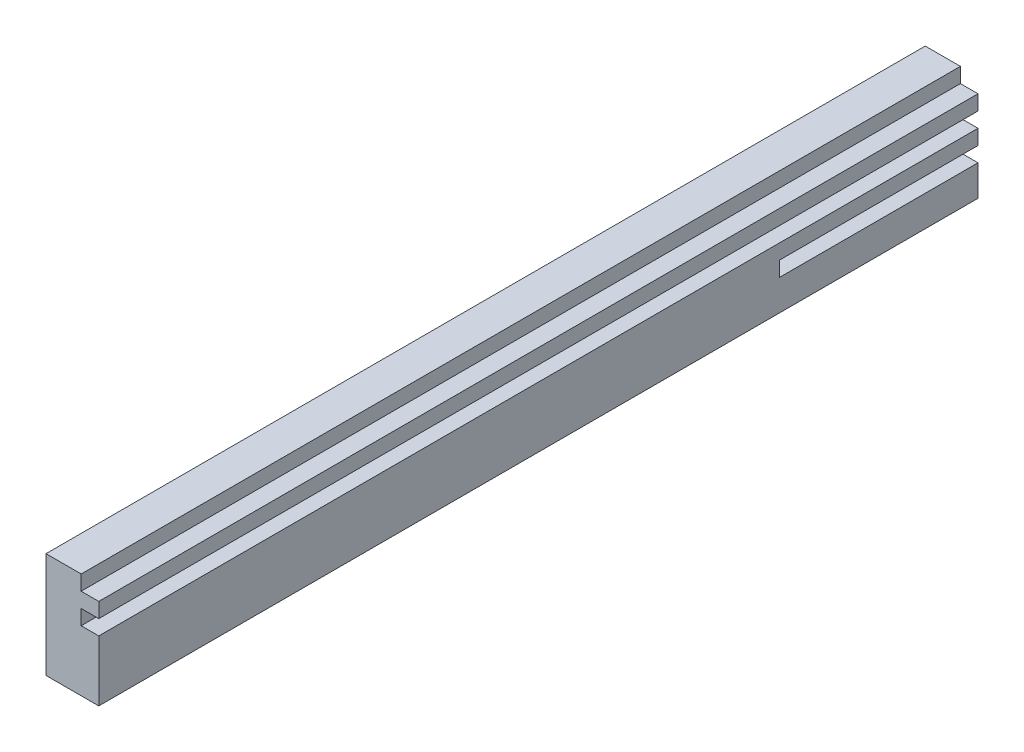
SolidWorks part; units mm, degrees
ref_plane "Front Plane" through (0, 0, 0) normal (0, 0, 1) x (1, 0, 0)
ref_plane "Top Plane" through (0, 0, 0) normal (0, 1, 0) x (1, 0, 0)
ref_plane "Right Plane" through (0, 0, 0) normal (1, 0, 0) x (0, 0, -1)
sketch "Sketch1" plane through (0, 0, 0) normal (1, 0, 0) x (0, 0, -1)
  line L1 (0, 0) -> (500, 0)
  line L2 (0, 0) -> (0, 60)
  line L3 (0, 60) -> (500, 60)
  line L4 (500, 0) -> (500, 60)
  dimension "D1" = 60
  dimension "D2" = 500
extrude "Boss-Extrude1" add sketch "Sketch1" along normal blind 30
sketch "Sketch2" plane through (30, 0, 0) normal (1, 0, 0) x (0, 0, -1)
  line L0 (500, 0) -> (500, 60) construction
  line L1 (0, 60) -> (500, 60)
  line L2 (0, 60) -> (0, 51.5)
  line L3 (0, 51.5) -> (500, 51.5)
  line L4 (500, 60) -> (500, 51.5)
  line L5 (0, 60) -> (0, 0) construction
  line L6 (0, 43) -> (500, 43)
  line L7 (0, 43) -> (0, 34.5)
  line L8 (0, 34.5) -> (500, 34.5)
  line L9 (500, 43) -> (500, 34.5)
  line L11 (500, 26) -> (387.1115, 26)
  line L12 (500, 26) -> (500, 17.5)
  line L13 (500, 17.5) -> (387.1115, 17.5)
  line L14 (387.1115, 26) -> (387.1115, 17.5)
  dimension "D1" = 8.5
  dimension "D2" = 8.5
  dimension "D3" = 8.5
  dimension "D4" = 8.5
  dimension "D5" = 8.5
extrude "Cut-Extrude1" cut sketch "Sketch2" against normal blind 10 contours L2 L1 L4 L3 | L7 L6 L9 L8 | L12 L11 L14 L13
